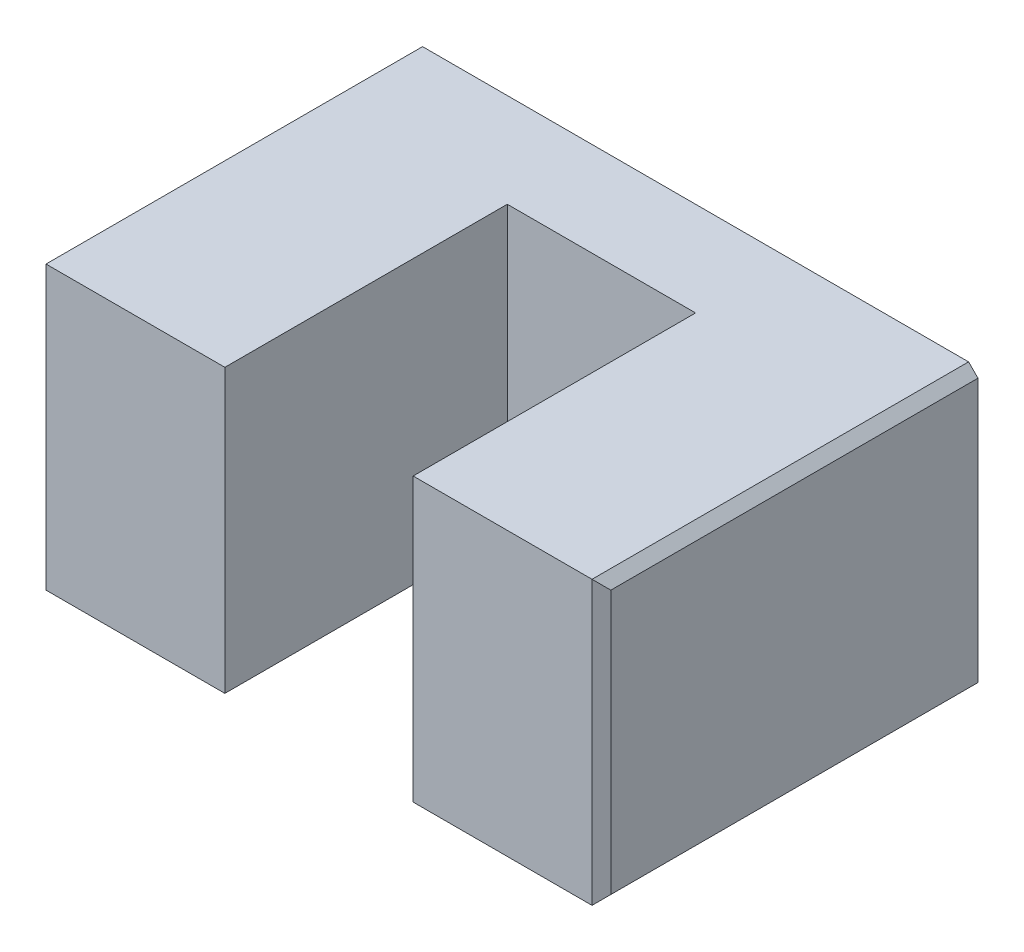
SolidWorks part; units mm, degrees
ref_plane "前视基准面" through (0, 0, 0) normal (0, 0, 1) x (1, 0, 0)
ref_plane "上视基准面" through (0, 0, 0) normal (0, 1, 0) x (1, 0, 0)
ref_plane "右视基准面" through (0, 0, 0) normal (1, 0, 0) x (0, 0, -1)
other "Configuration Table"
sketch "Sketch1" plane through (0, 0, 0) normal (0, 1, 0) x (1, 0, 0)
  line L0 (-30, 0) -> (-30, -40)
  line L1 (-30, -40) -> (-10, -40)
  line L2 (-10, -40) -> (-10, -10)
  line L3 (-10, -10) -> (10, -10)
  line L4 (10, -10) -> (10, -40)
  line L5 (10, -40) -> (30, -40)
  line L6 (30, -40) -> (30, 0)
  line L7 (30, 0) -> (-30, 0)
extrude "Boss-Extrude1" add sketch "Sketch1" along normal blind 30
sketch "Sketch2" plane through (0, 0, 0) normal (0, 0, 1) x (1, 0, 0)
  circle A0 centre (0, 0) radius 20
extrude "Boss-Extrude2" add sketch "Sketch2" along normal blind 5
sketch "Sketch3" plane through (0, 0, 0) normal (0, 0, 1) x (1, 0, 0)
  circle A0 centre (0, 0) radius 10
extrude "Cut-Extrude1" cut sketch "Sketch3" along normal blind 20
ref_plane "mount_bottom_face" through (0, 0, 0) normal (0, 0, 1) x (1, 0, 0)
sketch3d "3DSketch1"
  line L0 (0, 0, 0) -> (0, 0, 100) construction
ref_axis "mount_axis_z" through (0, 0, 0) along (0, 0, 1)
chamfer "Chamfer1" distance 1 angle 45 6 edges at (30, 30, 20) (30, 0, 20) (30, 15, 40) (-30, 30, 20) (-30, 0, 20) (-30, 15, 40)
